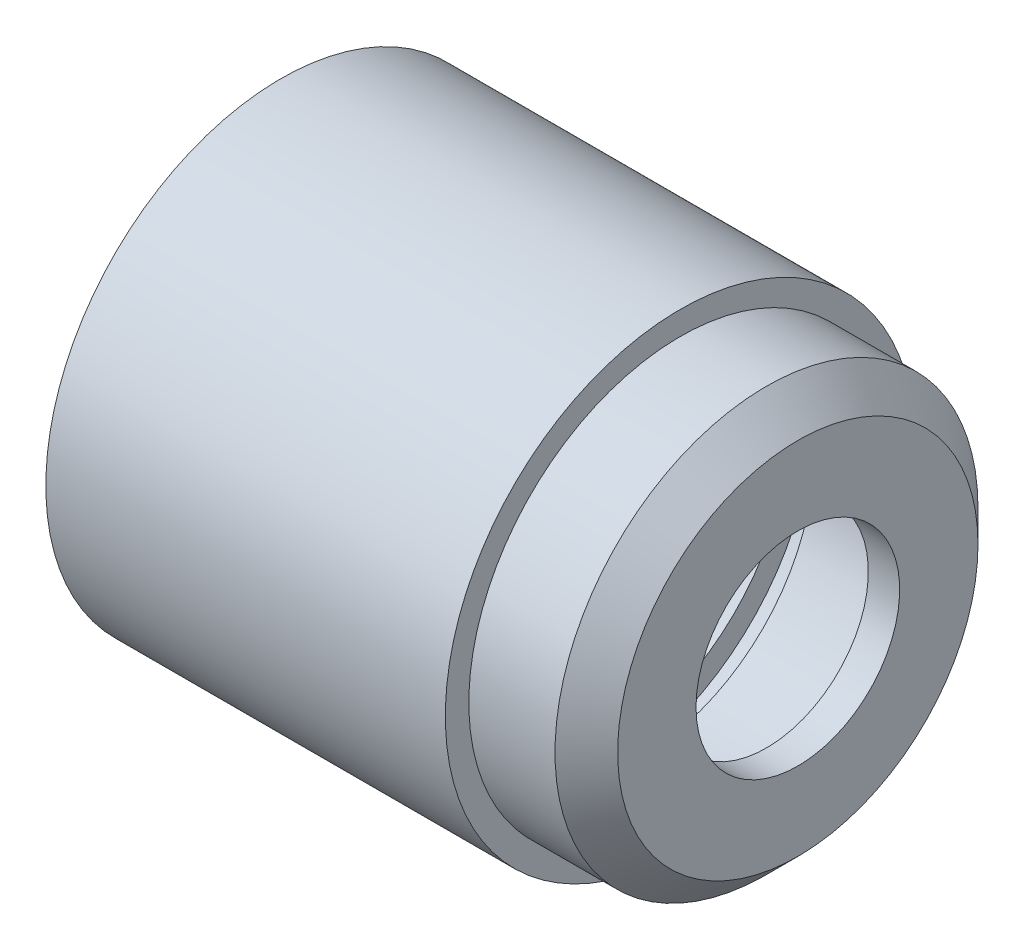
SolidWorks part; units mm, degrees
material "Alliage de zinc AC41A, brut"
ref_plane "Plan de face" through (0, 0, 0) normal (0, 0, 1) x (1, 0, 0)
ref_plane "Plan de dessus" through (0, 0, 0) normal (0, 1, 0) x (1, 0, 0)
ref_plane "Plan de droite" through (0, 0, 0) normal (1, 0, 0) x (0, 0, -1)
sketch "Sketch1" plane through (0, 0, 0) normal (1, 0, 0) x (0, 0, -1)
  circle A0 centre (0, 0) radius 15
  dimension "D1" = 30
extrude "Boss-Extrude1" add sketch "Sketch1" along normal blind 25.5
sketch "Sketch2" plane through (25.5, 0, 0) normal (1, 0, 0) x (0, 0, -1)
  circle A0 centre (0, 0) radius 13.5
  dimension "D1" = 27
extrude "Boss-Extrude2" add sketch "Sketch2" along normal blind 7.5
sketch "Sketch3" plane through (0, 0, 0) normal (-1, 0, 0) x (0, 0, 1)
  circle A0 centre (0, 0) radius 14
  dimension "D1" = 28
extrude "Cut-Extrude1" cut sketch "Sketch3" against normal blind 6.5
sketch "Sketch4" plane through (6.5, 0, 0) normal (-1, 0, 0) x (0, 0, 1)
  circle A0 centre (0, 0) radius 12
  dimension "D1" = 24
extrude "Cut-Extrude2" cut sketch "Sketch4" against normal blind 14
sketch "Sketch5" plane through (20.5, 0, 0) normal (-1, 0, 0) x (0, 0, 1)
  circle A0 centre (0, 0) radius 13.5
  dimension "D1" = 27
extrude "Cut-Extrude3" cut sketch "Sketch5" against normal blind 2.5
sketch "Sketch6" plane through (23, 0, 0) normal (-1, 0, 0) x (0, 0, 1)
  circle A0 centre (0, 0) radius 11
  dimension "D1" = 22
extrude "Cut-Extrude4" cut sketch "Sketch6" against normal blind 6
sketch "Sketch7" plane through (29, 0, 0) normal (-1, 0, 0) x (0, 0, 1)
  circle A0 centre (0, 0) radius 11.5
  dimension "D1" = 23
extrude "Cut-Extrude5" cut sketch "Sketch7" against normal blind 1
sketch "Sketch9" plane through (30, 0, 0) normal (-1, 0, 0) x (0, 0, 1)
  circle A0 centre (0, 0) radius 10
  dimension "D1" = 20
extrude "Cut-Extrude6" cut sketch "Sketch9" against normal blind 1
sketch "Sketch10" plane through (31, 0, 0) normal (-1, 0, 0) x (0, 0, 1)
  circle A0 centre (0, 0) radius 6.5
  dimension "D1" = 13
extrude "Cut-Extrude7" cut sketch "Sketch10" against normal blind 2
chamfer "Chamfer1" distance 2 angle 45 1 edges at (33, 0, -13.5)
